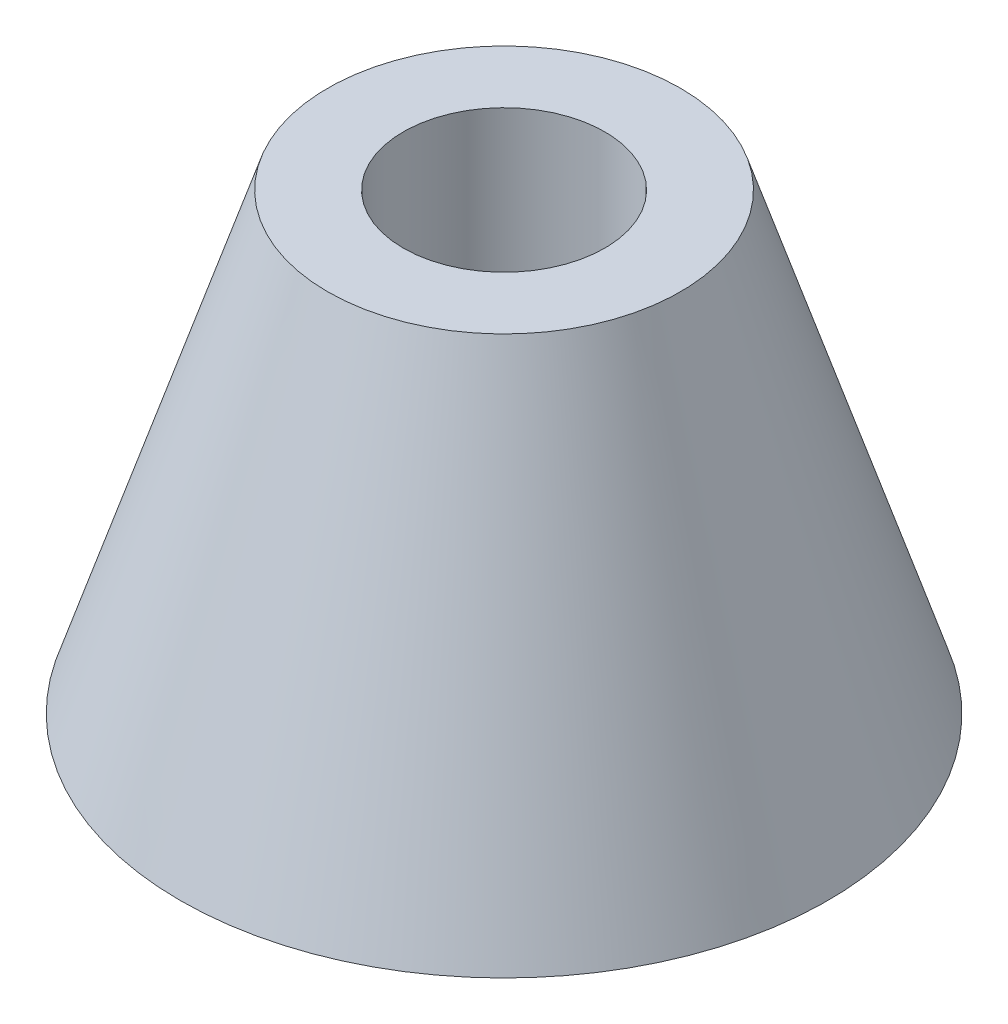
SolidWorks part; units mm, degrees
ref_plane "Спереди" through (0, 0, 0) normal (0, 0, 1) x (1, 0, 0)
ref_plane "Сверху" through (0, 0, 0) normal (0, 1, 0) x (1, 0, 0)
ref_plane "Справа" through (0, 0, 0) normal (1, 0, 0) x (0, 0, -1)
sketch "Sketch1" plane through (0, 0, 0) normal (0, 1, 0) x (1, 0, 0)
  circle A0 centre (0, 0) radius 2
  circle A1 centre (0, 0) radius 3.5
  dimension "D1" = 4
  dimension "D2" = 7
extrude "Extrude1" add sketch "Sketch1" along normal blind 9
draft "Draft7" type of draft neutral plane draft angle 18 faces to draft 1 face at (0, 9, 3.5) neutral plane through (0, 9, 0) neutral plane normal (0, 1, 0) parameters "D1"=18
